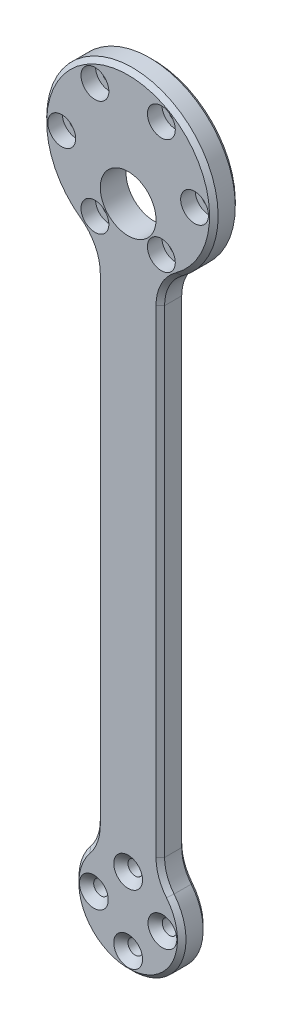
SolidWorks part; units mm, degrees
note: '?' marks a value the reader was unsure of.
material "1060 Alloy"
ref_plane "Front" through (0, 0, 0) normal (0, 0, 1) x (1, 0, 0)
ref_plane "Top" through (0, 0, 0) normal (0, 1, 0) x (1, 0, 0)
ref_plane "Right" through (0, 0, 0) normal (1, 0, 0) x (0, 0, -1)
sketch "Sketch1" plane through (0, 0, 0) normal (0, 0, 1) x (1, 0, 0)
  line L1 (-7.5, 75) -> (7.5, 75)
  line L2 (-7.5, 75) -> (-7.5, -75)
  line L3 (-7.5, -75) -> (7.5, -75)
  line L4 (7.5, 75) -> (7.5, -75)
  line L5 (-7.5, 75) -> (7.5, -75) construction
  line L6 (-7.5, -75) -> (7.5, 75) construction
  circle A0 centre (0, 75) radius 20
  circle A1 centre (0, -75) radius 12.5
  point P0 (0, 0)
  dimension "D3" = 20
  dimension "D4" = 25
  dimension "D1" = 150
  dimension "D2" = 15
extrude "Boss-Extrude1" add sketch "Sketch1" along normal blind 6 contours L4 A0 L2 L1 | L2 A0 L4 L1 | A0 L2 L3 L4 | L4 A1 L2 L3 | L2 A1 L4 L3
sketch "Sketch2" plane through (0, 0, 6) normal (0, 0, 1) x (1, 0, 0)
  arc A0 (7.5, 56.4595) -> (-7.5, 56.4595) centre (0, 75) ccw construction
  arc A1 (7.5, 56.4595) -> (-7.5, 56.4595) centre (0, 75) ccw
  circle A2 centre (0, 68) radius 6.5
  point P14 (0, 100.9234)
  point P16 (-29.4006, 48.1532)
  point P18 (-44.9006, 74.0766)
  point P20 (-30.2003, 100.4617)
  dimension "D2" = 13
  dimension "D3" = 7
extrude "Cut-Extrude1" cut sketch "Sketch2" against normal up to surface (6 mm away) contours A2 up to face at (0, -0.2601, 0)
fillet "Fillet1" radius 10 4 edges at (-7.5, 56.4595, 3) (7.5, 56.4595, 3) (7.5, -65, 3) (-7.5, -65, 3)
sketch "Sketch4" plane through (0, 0, 6) normal (0, 0, 1) x (1, 0, 0)
  arc A0 (11.6667, 58.7553) -> (-11.6667, 58.7553) centre (0, 75) ccw construction
  arc A1 (11.6667, 58.7553) -> (-11.6667, 58.7553) centre (0, 75) ccw
  point P3 (15.5, 75)
  dimension "D1" = 15.5
hole_wizard "CBORE for M3 Hex Socket Head Cap Screw2" positions "3DSketch2" profile "Sketch5" counterbore size "M3" standard "ISO"
sketch3d "3DSketch2"
  point P0 (15.5, 75, 6)
sketch "Sketch5" plane through (15.5, 75, 6) normal (1, 0, 0) x (0, -1, 0)
  line L0 (0, 0) -> (0, 7.0205)
  line L1 (0, 7.0205) -> (1.7, 5.999)
  line L2 (1.7, 5.999) -> (1.7, 3.4)
  line L3 (1.7, 3.4) -> (3.25, 3.4)
  line L4 (3.25, 3.4) -> (3.25, 0)
  line L5 (3.25, 0) -> (0, 0)
  line L10 (0, 7.0205) -> (-1.7, 5.999) construction
  line L11 (0, -6.35) -> (0, 107.95) construction
  dimension "Hole Dia." = 3.4
  dimension "Hole Depth" = 5.999
  dimension "C'Bore Dia." = 6.5
  dimension "C'Bore Depth" = 3.4
  dimension "Drill Angle" = 118
ref_axis "Axis1" through (0, 75, 6) along (0, 0, -1)?
pattern_circular "CirPattern1" count 6 over 360 about axis through (0, 75, 0) along (0, 0, 1) of "CBORE for M3 Hex Socket Head Cap Screw2"
sketch "Sketch6" plane through (0, 0, 6) normal (0, 0, 1) x (1, 0, 0)
  arc A0 (-9.7222, -67.1433) -> (9.7222, -67.1433) centre (0, -75) ccw construction
  arc A1 (-9.7222, -67.1433) -> (9.7222, -67.1433) centre (0, -75) ccw
  point P3 (8, -75)
  point P7 (0, -83)
  point P8 (-8, -75)
  point P9 (0, -67)
  dimension "D1" = 8
  dimension "D2" = 4
hole_wizard "CSK for M3 Hex Socket Countersunk Cap Screw1" positions "3DSketch3" profile "Sketch8" countersink size "M3" standard "ISO"
sketch3d "3DSketch3"
  point P0 (0, -67, 6)
  point P3 (8, -75, 6)
  point P6 (0, -83, 6)
  point P9 (-8, -75, 6)
sketch "Sketch8" plane through (0, -67, 6) normal (1, 0, 0) x (0, -1, 0)
  line L0 (0, 0) -> (0, 7.0205)
  line L1 (0, 7.0205) -> (1.7, 5.999)
  line L2 (1.7, 5.999) -> (1.7, 1.66)
  line L3 (1.7, 1.66) -> (3.36, 0)
  line L5 (3.36, 0) -> (0, 0)
  line L6 (-1.7, 1.66) -> (-3.36, 0) construction
  line L10 (0, 7.0205) -> (-1.7, 5.999) construction
  line L11 (0, -6.35) -> (0, 107.95) construction
  dimension "Hole Dia." = 3.4
  dimension "Hole Depth" = 5.999
  dimension "Near C'Sink Dia." = 6.72
  dimension "Near C'Sink Angle" = 90
  dimension "Drill Angle" = 118
chamfer "Chamfer1" distance 1 angle 45 16 edges at (7.5, -5.1124, 6) (7.5, -5.1124, 0) (-7.5, -5.1124, 0) (-7.5, -5.1124, 6) (8.6024, 55.1974, 6) (8.6024, 55.1974, 0) (-8.6024, 55.1974, 6) (-8.6024, 55.1974, 0) (0, 95, 0) (0, 95, 6) (0, -87.5, 0) (0, -87.5, 6) (8.0719, -64.1912, 6) (8.0719, -64.1912, 0) (-8.0719, -64.1912, 6) (-8.0719, -64.1912, 0)
equation "\"L\"= 150mm'Length"
equation "\"R\"= 20mm'Radius"
equation "\"D1@Sketch1\"=\"L\""
equation "\"W\"= 15mm'width"
equation "\"T\"= 6mm'Thickness"
equation "\"D2@Sketch1\"=\"W\""
equation "\"D3@Sketch1\"=\"R\""
equation "\"D1@Boss-Extrude1\"=\"T\""
equation "\"C\"= 1mm'chamfer and fillet"
